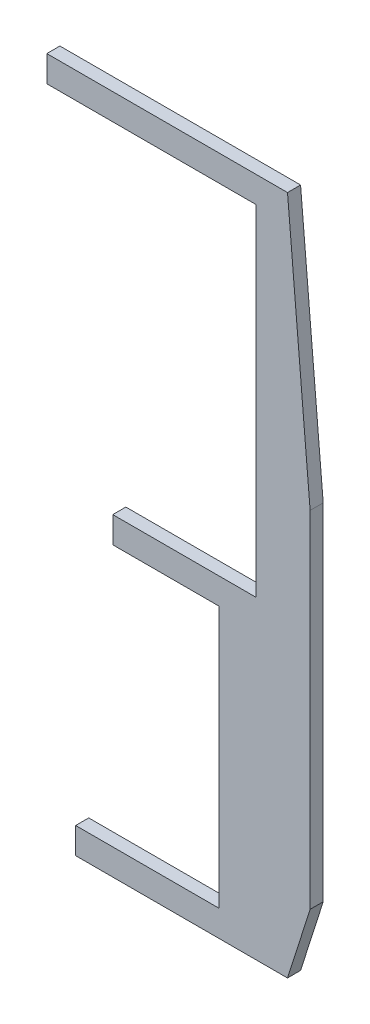
SolidWorks part; units mm, degrees
ref_plane "Front Plane" through (0, 0, 0) normal (0, 0, 1) x (1, 0, 0)
ref_plane "Top Plane" through (0, 0, 0) normal (0, 1, 0) x (1, 0, 0)
ref_plane "Right Plane" through (0, 0, 0) normal (1, 0, 0) x (0, 0, -1)
sketch "Sketch1" plane through (0, 0, 0) normal (0, 0, 1) x (1, 0, 0)
  line L0 (0, 0) -> (50.8, 0)
  line L1 (50.8, 0) -> (50.8, -82.55)
  line L2 (50.8, -82.55) -> (16.0069, -82.55)
  line L3 (16.0069, -82.55) -> (16.0069, -88.9)
  line L10 (63.9083, -57.7192) -> (58.42, 6.35)
  line L11 (58.42, 6.35) -> (0, 6.35)
  line L12 (0, 6.35) -> (0, 0)
  line L15 (63.9083, -141.5754) -> (63.9083, -57.7192)
  line L17 (16.0069, -88.9) -> (41.796, -88.9)
  line L18 (41.796, -88.9) -> (41.796, -152.4)
  line L19 (41.796, -152.4) -> (7.003, -152.4)
  line L20 (7.003, -152.4) -> (7.003, -158.75)
  line L21 (7.003, -158.75) -> (58.42, -158.75)
  line L22 (58.42, -158.75) -> (63.9083, -141.5754)
  dimension "D1" = 6.35
  dimension "D2" = 6.35
  dimension "D3" = 6.35
  dimension "D4" = 82.55
  dimension "D5" = 50.8
  dimension "D6" = 58.42
  dimension "D7" = 63.5
extrude "Boss-Extrude1" add sketch "Sketch1" along normal blind 3.175 contours L11 L12 L0 L1 L2 L3 L17 L18 L19 L20 L21 L22 L15 L10
